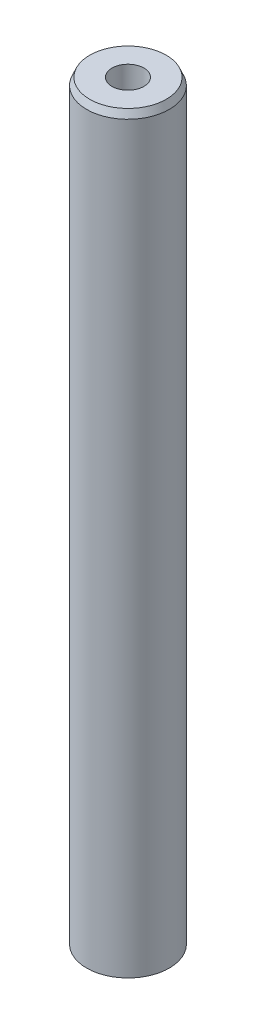
SolidWorks part; units mm, degrees
ref_plane "Front Plane" through (0, 0, 0) normal (0, 0, 1) x (1, 0, 0)
ref_plane "Top Plane" through (0, 0, 0) normal (0, 1, 0) x (1, 0, 0)
ref_plane "Right Plane" through (0, 0, 0) normal (1, 0, 0) x (0, 0, -1)
sketch "Sketch1" plane through (0, 0, 0) normal (0, 1, 0) x (1, 0, 0)
  circle A0 centre (0, 0) radius 7.5
  dimension "SHAFT_OD" = 15
extrude "Boss-Extrude1" add sketch "Sketch1" along normal blind 136.81
sketch "Sketch2" plane through (0, 0, 0) normal (0, 1, 0) x (1, 0, 0)
  circle A0 centre (0, 0) radius 2.8954
  dimension "BORE_D" = 5.7908
extrude "Cut-Extrude1" cut sketch "Sketch2" along normal through all
chamfer "Chamfer1" distance 1.3094 angle 23.1 2 edges at (0, 136.81, 7.5) (0, 0, 7.5) first distance on face at (0, 136.81, 7.5) first distance on face at (0, 0, 2.8954)
